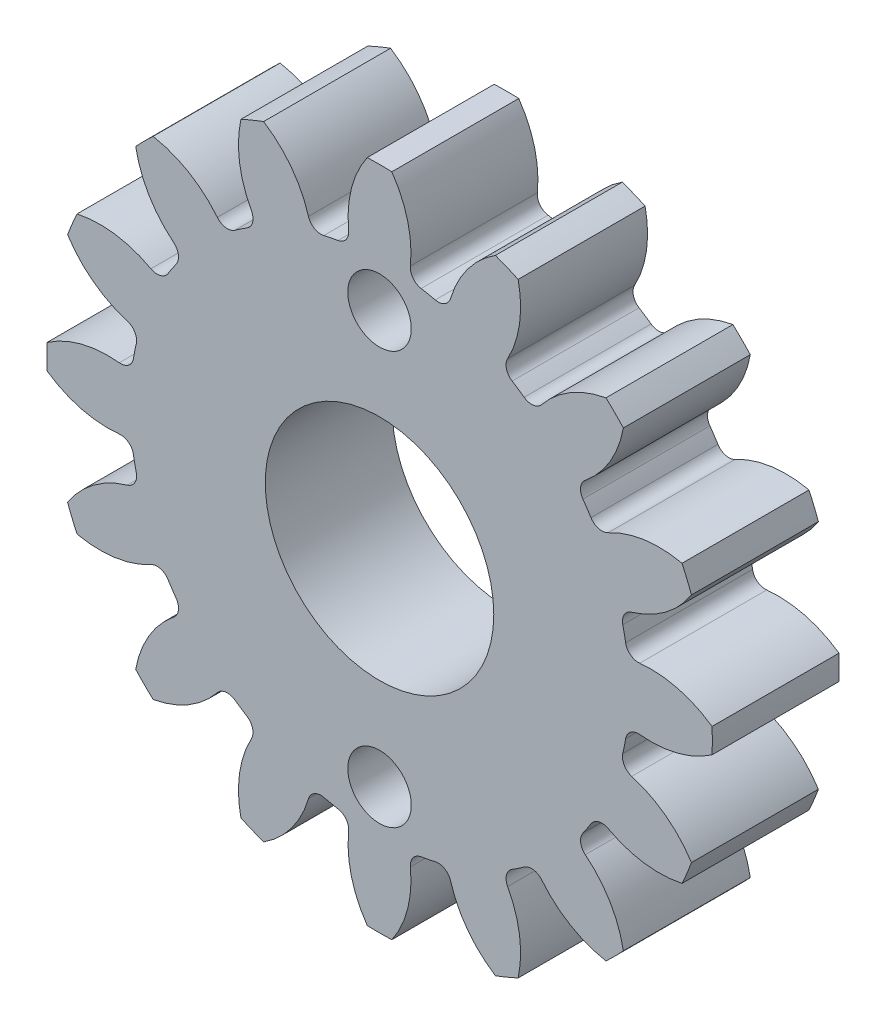
SolidWorks part; units mm, degrees
material "ABS"
ref_plane "Plane1" through (0, 0, 0) normal (0, 0, 1) x (1, 0, 0)
ref_plane "Plane2" through (0, 0, 0) normal (0, 1, 0) x (1, 0, 0)
ref_plane "Plane3" through (0, 0, 0) normal (1, 0, 0) x (0, 0, -1)
sketch "Esquisse1" plane through (0, 0, 0) normal (0, 0, 1) x (1, 0, 0)
  circle A0 centre (0, 0) radius 1.15
  dimension "D1" = 2.3
extrude "Base-Extrusion" add sketch "Esquisse1" along normal blind 2.5
sketch "Parametres" plane through (0, 0, 2.5) normal (0, 0, 1) x (1, 0, 0)
  line L0 (-33.4711, 41.7411) -> (-17.4711, 41.7411)
  line L1 (-33.4711, 34.0759) -> (-32.3061, 34.0759)
  line L2 (-33.4711, 23.0892) -> (-13.4711, 23.0892)
  line L3 (-33.4711, -2.6579) -> (-33.1221, -2.6579)
  line L4 (-38.9094, -12.5583) -> (-35.7678, -12.5583)
  line L5 (-48.8826, -19.2556) -> (-39.5626, -19.2556)
  line L6 (-48.8826, -29.9283) -> (-38.3976, -29.9283)
  line L7 (-48.8826, -38.2322) -> (-41.0188, -38.2322)
  line L8 (-48.8826, -45.1309) -> (-40.1246, -45.1309)
  line L9 (-48.8826, -60.7647) -> (-47.0526, -60.7647)
  line L10 (-48.8826, -76.1039) -> (-46.9019, -76.1039)
  line L11 (-48.8826, -88.0795) -> (-48.3004, -88.0795)
  line L12 (-50.5648, -98.8973) -> (-51.3404, -98.8973)
  line L13 (16.9123, -61.9871) -> (28.1623, -61.9871)
  line L14 (18.5152, -81.0212) -> (31.4731, -81.0212)
  line L15 (8.671, -96.0481) -> (4.433, -96.0481)
  line L16 (-33.4711, 13.8609) -> (-21.4711, 13.8609)
sketch "Esquisse3" plane through (0, 0, 0) normal (0, 0, 1) x (1, 0, 0)
  line L0 (0, 0) -> (0, 29.3764) construction
  line L1 (-1.5341, 7.7127) -> (0, 0)
  line L2 (0, 0) -> (1.5341, 7.7127)
  line L3 (0, 0) -> (0.9882, 8.702) construction
  line L4 (0, 0) -> (0.3877, 10.4778) construction
  line L5 (0, 0) -> (0.9135, 9.2751) construction
  arc A0 (0.3877, 10.4778) -> (0.908, 7.8112) centre (-2.3706, 8.5556) cw
  arc A1 (-0.3877, 10.4778) -> (-0.908, 7.8112) centre (2.3706, 8.5556) ccw
  arc A2 (1.5341, 7.7127) -> (0.908, 7.8112) centre (0, 0) ccw
  arc A3 (-1.5341, 7.7127) -> (-0.908, 7.8112) centre (0, 0) cw
  arc A4 (0.3877, 10.4778) -> (-0.3877, 10.4778) centre (0, 0) ccw
  dimension "D4" = 22.5
  dimension "D5" = 8.7579
  dimension "D6" = 9.32
  dimension "D1" = 10.485
  dimension "D2" = 6.479
  dimension "D3" = 5.625
  dimension "D7" = 2.119
  dimension "D8" = 7.8638
extrude "Boss.-Extru.1" add sketch "Esquisse3" along normal blind 4
fillet "Congé1" radius 0.4078 2 edges at (0.908, 7.8112, 2) (-0.908, 7.8112, 2)
ref_axis "Axe1" through (0, 0, 54) along (0, 0, -1)
pattern_circular "Répétition circulaire4" count 16 every 22.5 about axis through (0, 0, 54) along (0, 0, -1) of "Boss.-Extru.1", "Congé1"
sketch "Esquisse8" plane through (0, 0, 4) normal (0, 0, 1) x (1, 0, 0)
  circle A0 centre (0, 0) radius 3.6
  dimension "D1" = 7.2
extrude "Enlèv. mat.-Extru.1" cut sketch "Esquisse8" against normal through all
sketch "Esquisse9" plane through (0, 0, 0) normal (0, 0, -1) x (-1, 0, 0)
  line L0 (0, 6.5) -> (0, -6.5) construction
  circle A0 centre (0, 6.5) radius 1
  circle A1 centre (0, -6.5) radius 1
  dimension "D2" = 2
  dimension "D1" = 13
extrude "Enlèv. mat.-Extru.2" cut sketch "Esquisse9" against normal through all
equation "\"PI@Parametres\" = 3.141592654"
equation "\"Alpha_rad@Parametres\" = \"Alpha@Parametres\"*\"PI@Parametres\"/180"
equation "\"R@Parametres\" = \"Z@Parametres\"*\"m@Parametres\"/2"
equation "\"RT@Parametres\" = \"R@Parametres\"+\"m@Parametres\""
equation "\"RP@Parametres\" = \"R@Parametres\"-1.25*\"m@Parametres\""
equation "\"Rb@Parametres\" = \"R@Parametres\"*cos(\"Alpha_rad@Parametres\")"
equation "\"E@Parametres\" = \"PI@Parametres\"*\"R@Parametres\"/\"Z@Parametres\""
equation "\"Eb@Parametres\" = \"Rb@Parametres\"*((\"PI@Parametres\"*\"m@Parametres\"/(2*\"R@Parametres\"))+2*(tan(\"Alpha_rad@Parametres\")-\"Alpha_rad@Parametres\"))"
equation "\"As@Parametres\" = atn(sqr(\"RT@Parametres\"*\"RT@Parametres\"-\"Rb@Parametres\"*\"Rb@Parametres\")/\"Rb@Parametres\")"
equation "\"Et@Parametres\" = \"RT@Parametres\"*((\"E@Parametres\"/\"R@Parametres\")+2*(tan(\"Alpha_rad@Parametres\")-\"Alpha_rad@Parametres\"-tan(\"As@Parametres\")+\"As@Parametres\"))"
equation "\"Ap@Parametres\" = (\"E@Parametres\"/\"R@Parametres\")*180/\"PI@Parametres\""
equation "\"Ab@Parametres\" = (\"Eb@Parametres\"/\"Rb@Parametres\")*180/\"PI@Parametres\""
equation "\"At@Parametres\" = (\"Et@Parametres\"/\"RT@Parametres\")*180/\"PI@Parametres\""
equation "\"D7@Esquisse3\" = \"At@Parametres\"/2"
equation "\"D3@Esquisse3\"=\"Ap@Parametres\"/2"
equation "\"D2@Esquisse3\"=\"Ab@Parametres\"/2"
equation "\"D5@Esquisse3\"=\"Rb@Parametres\""
equation "\"D6@Esquisse3\"=\"R@Parametres\""
equation "\"D1@Esquisse3\"=\"RT@Parametres\""
equation "\"D4@Esquisse3\" = \"Ap@Parametres\"*2"
equation "\"D1@Congé1\" = 0.35*\"m@Parametres\""
equation "\"D2@Répétition circulaire4\" = \"Ap@Parametres\"*2"
equation "\"D1@Répétition circulaire4\" = \"Z@Parametres\""
equation "\"D8@Esquisse3\" = \"RP@Parametres\""
